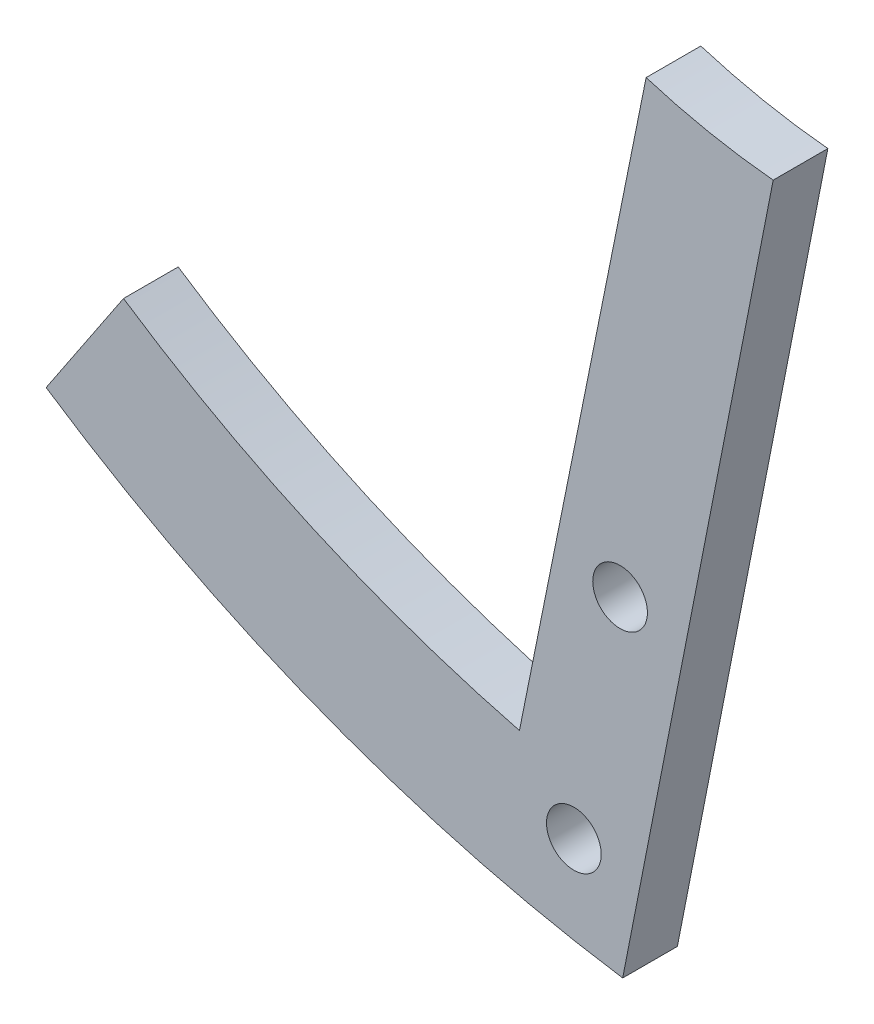
SolidWorks part; units mm, degrees
ref_plane "Front" through (0, 0, 0) normal (0, 0, 1) x (1, 0, 0)
ref_plane "Top" through (0, 0, 0) normal (0, 1, 0) x (1, 0, 0)
ref_plane "Right" through (0, 0, 0) normal (1, 0, 0) x (0, 0, -1)
ref_axis "Axis1" through (0, 0, -80.9) along (0, 0, 1)
sketch "草图1" plane through (0, 0, 0) normal (0, 0, 1) x (1, 0, 0)
  circle A0 centre (0, 0) radius 18
extrude "LaShenA" add sketch "草图1" along normal blind 3
sketch "SketchA" plane through (0, 0, 3) normal (0, 0, 1) x (1, 0, 0)
  line L0 (0, 0) -> (0, 18) construction
  arc A0 (0.4232, 13.4934) -> (-0.4232, 13.4934) centre (0, 0) ccw
  arc A1 (3.858, 18.7275) -> (-3.858, 18.7275) centre (0, 0) ccw
  arc A2 (-0.4232, 13.4934) -> (-1.2044, 14.1898) centre (-0.447, 14.253) cw
  arc A3 (1.2044, 14.1898) -> (0.4232, 13.4934) centre (0.447, 14.253) cw
  circle A4 centre (0, 0) radius 15.0351 construction
  circle A5 centre (0, 0) radius 18 construction
  circle A6 centre (0, 0) radius 13.5 construction
  circle A7 centre (0, 0) radius 16 construction
  spline S0 degree 3 poles (1.2044, 14.1898) (1.2266, 14.4552) (1.2138, 14.7739) (1.2737, 15.1106) (1.2991, 15.2114) (1.3214, 15.2911) (1.3499, 15.3823) (1.3851, 15.4846) (1.4278, 15.5978) (1.4786, 15.7214) (1.5382, 15.8552) (1.6071, 15.9987) (1.686, 16.1514) (1.7754, 16.3129) (1.876, 16.4827) (1.9884, 16.6603) (2.1129, 16.8451) (2.2502, 17.0365) (2.4007, 17.234) (2.5649, 17.4369) (2.7432, 17.6446) (2.9361, 17.8564) (3.1439, 18.0718) (3.4474, 18.3685) (3.6895, 18.585) (3.858, 18.7275) knots 0.122308 0.122308 0.122308 0.122308 0.250611 0.276296 0.287604 0.300968 0.316388 0.333864 0.353395 0.374983 0.398627 0.424327 0.452082 0.481894 0.513762 0.547685 0.583665 0.6217 0.661792 0.703939 0.748143 0.794402 0.842718 0.893089 1 1 1 1
  spline S1 degree 3 poles (-1.2044, 14.1898) (-1.2266, 14.4552) (-1.2138, 14.7739) (-1.2737, 15.1106) (-1.2991, 15.2114) (-1.3214, 15.2911) (-1.3499, 15.3823) (-1.3851, 15.4846) (-1.4278, 15.5978) (-1.4786, 15.7214) (-1.5382, 15.8552) (-1.6071, 15.9987) (-1.686, 16.1514) (-1.7754, 16.3129) (-1.876, 16.4827) (-1.9884, 16.6603) (-2.1129, 16.8451) (-2.2502, 17.0365) (-2.4007, 17.234) (-2.5649, 17.4369) (-2.7432, 17.6446) (-2.9361, 17.8564) (-3.1439, 18.0718) (-3.4474, 18.3685) (-3.6895, 18.585) (-3.858, 18.7275) knots 0.122308 0.122308 0.122308 0.122308 0.250611 0.276296 0.287604 0.300968 0.316388 0.333864 0.353395 0.374983 0.398627 0.424327 0.452082 0.481894 0.513762 0.547685 0.583665 0.6217 0.661792 0.703939 0.748143 0.794402 0.842718 0.893089 1 1 1 1
  dimension "D1" = 0.76
  dimension "Db" = 30.0702
  dimension "Da" = 36
  dimension "Df" = 27
  dimension "Dn" = 32
extrude "Cut-ExtrudeA" cut sketch "SketchA" against normal blind 3
pattern_circular "www.KYTool.cn" count 16 over 360 about axis through (0, 0, -80.9) along (0, 0, 1) of "Cut-ExtrudeA"
sketch "草图3" plane through (0, 0, 0) normal (0, 0, -1) x (-1, 0, 0)
  circle A0 centre (0, 0) radius 1.5
extrude "切除-拉伸2" cut sketch "草图3" against normal blind 10
sketch "草图4" plane through (0, 0, 0) normal (0, 0, -1) x (-1, 0, 0)
  line L0 (0, 0) -> (5, 0)
  circle A0 centre (5, 0) radius 1.5
  circle A1 centre (0, -5) radius 1.5
  circle A2 centre (-5, 0) radius 1.5
  circle A3 centre (0, 5) radius 1.5
  point P13 (0, 0)
  dimension "D1" = 4
extrude "切除-拉伸3" cut sketch "草图4" against normal blind 10 contours A3 | A0 | A1 | A2 region at (-5, -1.4576, 0) region at (0, -5, 0) region at (5, 0, 0) region at (0, 5, 0)
sketch "草图5" plane through (0, 0, 3) normal (0, 0, 1) x (1, 0, 0)
  line L0 (0, 0) -> (-5.1662, -12.4724)
  line L1 (-5.1662, -12.4724) -> (-6.8883, -16.6298)
  line L2 (0, 0) -> (0, -13.5)
  line L3 (0, -13.5) -> (0, -18)
  line L4 (-6.8883, -16.6298) -> (0, -18)
  line L5 (0, 0) -> (-3.4442, -17.3149)
  line L6 (0, 0) -> (-1.7221, -8.6575)
  line L7 (-1.7221, -8.6575) -> (-9.5221, -47.8708)
  line L8 (-3.4442, -17.3149) -> (0, -18)
  line L9 (-3.4442, -17.3149) -> (-9.0102, -45.2973)
  line L10 (0, -18) -> (-5.566, -45.9824)
  line L11 (-9.0102, -45.2973) -> (-5.566, -45.9824)
  line L12 (0, -18) -> (-11.5627, -76.8753)
  line L13 (-6.8883, -16.6298) -> (-12.4543, -44.6122)
  line L14 (-6.8883, -16.6298) -> (-18.7364, -75.4484)
  line L15 (-10.5445, -14.5881) -> (-9.4425, -15.3245)
  line L16 (0, 0) -> (-9.9935, -14.9563)
  line L18 (-43.19, -64.6385) -> (-38.9455, -58.286)
  circle A0 centre (0, 0) radius 18
  arc A1 (-5.5547, -12.3043) -> (-4.7727, -12.6282) centre (0, 0) ccw construction
  arc A2 (-0.4232, -13.4934) -> (0.4232, -13.4934) centre (0, 0) ccw construction
  circle A3 centre (0, 0) radius 77.74
  circle A4 centre (0, 0) radius 70.1
  circle A5 centre (0, 0) radius 9.0989
extrude "凸台-拉伸1" add sketch "草图5" against normal blind 3 contours A5 L7 L4 L3 L2 | A5 L0 L1 L4 L7 | L7 A0 L4 | L4 A0 L7 | L14 A4 L12 L10 L11 L9 A0 | A0 L9 L11 L10 | A4 L14 A3 L12 | A4 L18 A3 L14 region at (-4.0434, -13.2766, 3) region at (-1.3451, -13.8133, 3) region at (-10.0924, -47.4643, 3) region at (-4.7644, -17.1935, 3) region at (-2.1779, -17.708, 3) region at (-4.5241, -31.7624, 3) region at (-14.4158, -72.4733, 3) region at (-29.8465, -67.3114, 3)
sketch "草图6" plane through (0, 0, 0) normal (0, 0, -1) x (-1, 0, 0)
  line L0 (0, -13.5) -> (5.1662, -12.4724)
  line L1 (0, 0) -> (2.5831, -12.9862)
  circle A1 centre (14.2416, -71.5973) radius 1.5
  circle A3 centre (11.7054, -58.8471) radius 1.5
extrude "切除-拉伸4" cut sketch "草图6" against normal blind 3 contours A3 | A1
sketch "草图7" plane through (0, 0, 0) normal (0, 0, -1) x (-1, 0, 0)
  circle A0 centre (0, 0) radius 35
extrude "切除-拉伸5" cut sketch "草图7" against normal blind 3
